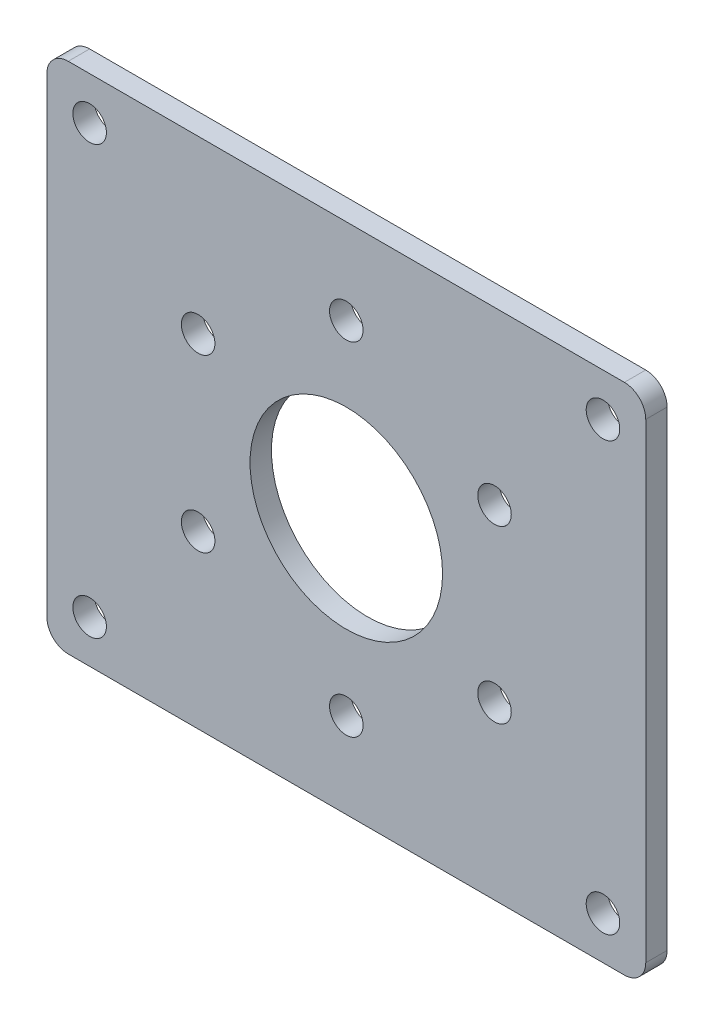
SolidWorks part; units mm, degrees
material "6061-T6 (SS)"
ref_plane "Front Plane" through (0, 0, 0) normal (0, 0, 1) x (1, 0, 0)
ref_plane "Top Plane" through (0, 0, 0) normal (0, 1, 0) x (1, 0, 0)
ref_plane "Right Plane" through (0, 0, 0) normal (1, 0, 0) x (0, 0, -1)
sketch "Sketch1" plane through (0, 0, 0) normal (0, 0, 1) x (1, 0, 0)
  line L0 (-38.1, -31.75) -> (-38.1, 31.75) construction
  line L1 (-44.45, -38.1) -> (44.45, -38.1)
  line L2 (-44.45, -38.1) -> (-44.45, 38.1)
  line L3 (-44.45, 38.1) -> (44.45, 38.1)
  line L4 (44.45, -38.1) -> (44.45, 38.1)
  line L5 (-44.45, -38.1) -> (44.45, 38.1) construction
  line L6 (-44.45, 38.1) -> (44.45, -38.1) construction
  line L7 (-38.1, 31.75) -> (38.1, 31.75) construction
  line L8 (38.1, -31.75) -> (38.1, 31.75) construction
  line L9 (-38.1, -31.75) -> (38.1, -31.75) construction
  circle A0 centre (0, 0) radius 30
  circle A1 centre (0, 25.4) radius 2.4892
  circle A2 centre (0, 0) radius 25.4 construction
  circle A3 centre (21.997, 12.7) radius 2.4892
  circle A4 centre (21.997, -12.7) radius 2.4892
  circle A5 centre (0, -25.4) radius 2.4892
  circle A6 centre (-21.997, -12.7) radius 2.4892
  circle A7 centre (-21.997, 12.7) radius 2.4892
  circle A8 centre (0, 0) radius 14.2875
  circle A9 centre (-38.1, 31.75) radius 2.4892
  circle A10 centre (-38.1, -31.75) radius 2.4892
  circle A11 centre (38.1, -31.75) radius 2.4892
  circle A12 centre (38.1, 31.75) radius 2.4892
  point P0 (0, 0)
  point P24 (0, 0)
  dimension "D1" = 60
  dimension "D2" = 4.9784
  dimension "D3" = 50.8
  dimension "D6" = 28.575
  dimension "D8" = 4.9784
  dimension "D5" = 88.9
  dimension "D9" = 76.2
  dimension "D7" = 6.35
  dimension "D4" = 6
extrude "Boss-Extrude1" add sketch "Sketch1" along normal blind 3.175 contours L1 L4 L3 L2 A12 A11 A10 A9 A0 | A0 A8 A7 A6 A5 A4 A3 A1 region at (-43.2791, 0, 0) region at (-29.1515, 0, 0)
fillet "Fillet1" radius 3.175 4 edges at (-44.45, -38.1, 1.5875) (44.45, 38.1, 1.5875) (44.45, -38.1, 1.5875) (-44.45, 38.1, 1.5875)
